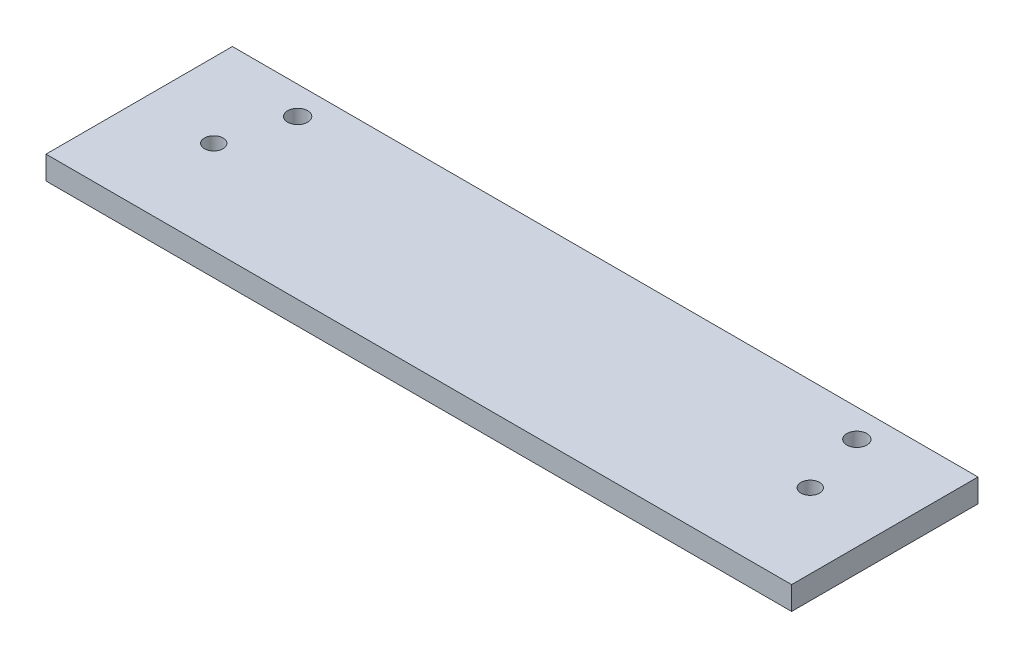
SolidWorks part; units mm, degrees
ref_plane "Front Plane" through (0, 0, 0) normal (0, 0, 1) x (1, 0, 0)
ref_plane "Top Plane" through (0, 0, 0) normal (0, 1, 0) x (1, 0, 0)
ref_plane "Right Plane" through (0, 0, 0) normal (1, 0, 0) x (0, 0, -1)
sketch "SK_Plate" plane through (0, 0, 0) normal (0, 1, 0) x (1, 0, 0)
  line L1 (-80, 20) -> (80, 20)
  line L2 (-80, 20) -> (-80, -20)
  line L3 (-80, -20) -> (80, -20)
  line L4 (80, 20) -> (80, -20)
  dimension "D1" = 40
  dimension "D2" = 160
  dimension "D3" = 20
  dimension "D4" = 80
extrude "EX_Plate" add sketch "SK_Plate" along normal blind 5
sketch "SK_PadPockets" plane through (0, 0, 0) normal (0, 1, 0) x (1, 0, 0)
  line L1 (51, 10) -> (77, 10)
  line L2 (51, 10) -> (51, -10)
  line L3 (51, -10) -> (77, -10)
  line L4 (77, 10) -> (77, -10)
  line L6 (-77, 10) -> (-51, 10)
  line L7 (-77, 10) -> (-77, -10)
  line L8 (-77, -10) -> (-51, -10)
  line L9 (-51, 10) -> (-51, -10)
  dimension "D1" = 20
  dimension "D2" = 26
  dimension "D3" = 10
  dimension "D4" = 51
  dimension "D5" = 20
  dimension "D6" = 26
  dimension "D7" = 10
  dimension "D8" = 77
extrude "CUT_PadPockets" cut sketch "SK_PadPockets" along normal blind 1
sketch "SK_PadInserts_M3" plane through (0, 0, 0) normal (0, 1, 0) x (1, 0, 0)
  circle A0 centre (64, 0) radius 2
  circle A1 centre (-64, 0) radius 2
  dimension "D2" = 4
  dimension "D4" = 4
  dimension "D1" = 64
  dimension "D3" = 64
extrude "CUT_PadInserts_M3" cut sketch "SK_PadInserts_M3" along normal blind 5
sketch "SK_Magnet" plane through (0, 0, 0) normal (0, 1, 0) x (1, 0, 0)
  circle A0 centre (0, 0) radius 3
  dimension "D1" = 6
extrude "CUT_Magnet" cut sketch "SK_Magnet" along normal blind 3
sketch "SK_FrameBolts" plane through (0, 0, 0) normal (0, 1, 0) x (1, 0, 0)
  circle A0 centre (60, 14) radius 2.15
  circle A1 centre (-60, 14) radius 2.15
  dimension "D3" = 4.3
  dimension "D6" = 4.3
  dimension "D1" = 14
  dimension "D2" = 60
  dimension "D4" = 14
  dimension "D5" = 60
extrude "CUT_FrameBolts" cut sketch "SK_FrameBolts" along normal blind 5
ref_axis "AX_X" through (0, 0, -22) along (0, 0, 1)
ref_axis "AX_Y" through (88, 0, 0) along (-1, 0, 0)
ref_axis "AX_Z" through (0, 5.25, 0) along (0, -1, 0)
sketch "SK_F_IF_PadL" plane through (0, 0, 0) normal (0, 1, 0) x (1, 0, 0)
  point P0 (64, 0)
  dimension "D1" = 64
sketch "SK_F_IF_PadR" plane through (0, 0, 0) normal (0, 1, 0) x (1, 0, 0)
  point P0 (-64, 0)
  dimension "D1" = 64
